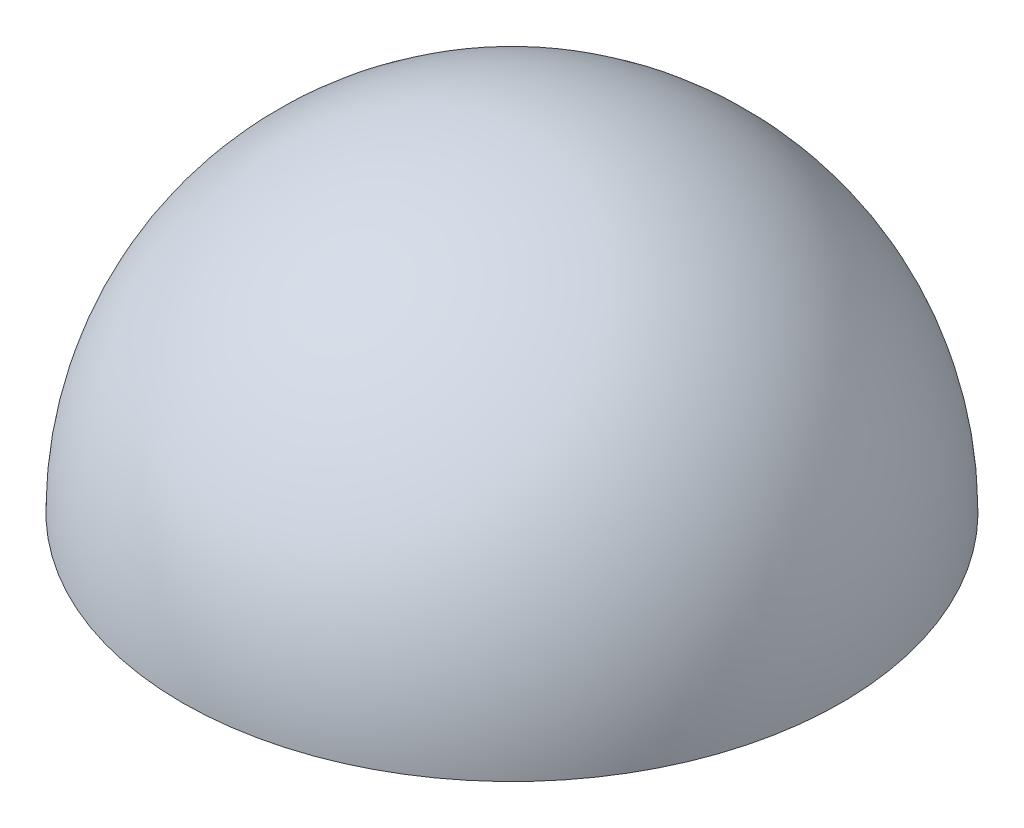
SolidWorks part; units mm, degrees
ref_plane "前视基准面" through (0, 0, 0) normal (0, 0, 1) x (1, 0, 0)
ref_plane "上视基准面" through (0, 0, 0) normal (0, 1, 0) x (1, 0, 0)
ref_plane "右视基准面" through (0, 0, 0) normal (1, 0, 0) x (0, 0, -1)
other "Configuration Table"
sketch "草图1" plane through (0, 0, 0) normal (0, 0, 1) x (1, 0, 0)
  line L0 (-50, 0) -> (50, 0) construction
  line L1 (-50, 0) -> (50, 0)
  arc A0 (50, 0) -> (-50, 0) centre (0, 0) ccw
  dimension "D1" = 100
revolve "旋转1" add sketch "草图1" angle 360 about L0
sketch "草图2" plane through (0, 0, 0) normal (0, 0, 1) x (1, 0, 0)
  line L1 (-63.0644, 0) -> (63.5414, 0)
  line L2 (-63.0644, 0) -> (-63.0644, -54.2392)
  line L3 (-63.0644, -54.2392) -> (63.5414, -54.2392)
  line L4 (63.5414, 0) -> (63.5414, -54.2392)
extrude "切除-拉伸1" cut sketch "草图2" against normal through all and the other way through all
shell "抽壳1" thickness 10 removed face at (0, 0, 50)
